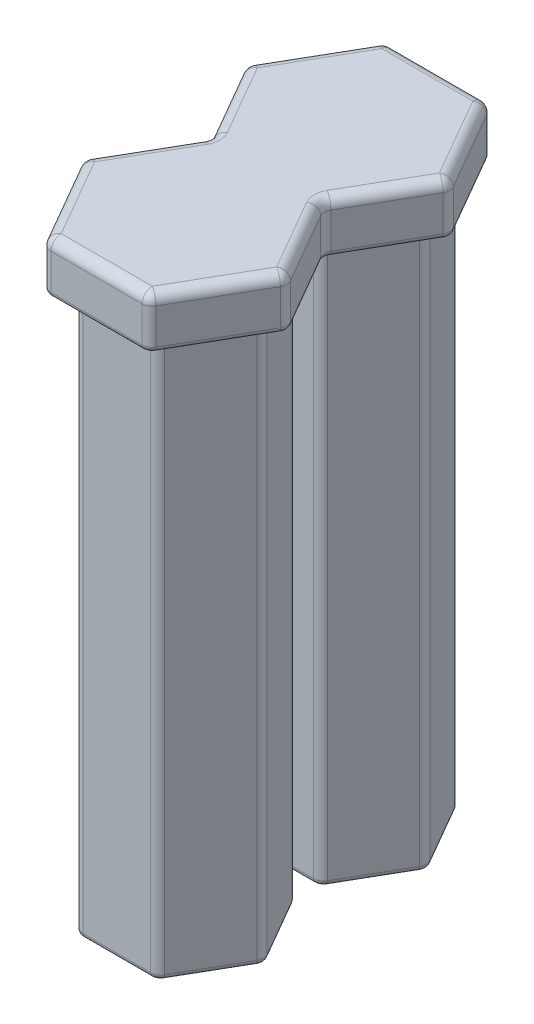
SolidWorks part; units mm, degrees
ref_plane "Front Plane" through (0, 0, 0) normal (0, 0, 1) x (1, 0, 0)
ref_plane "Top Plane" through (0, 0, 0) normal (0, 1, 0) x (1, 0, 0)
ref_plane "Right Plane" through (0, 0, 0) normal (1, 0, 0) x (0, 0, -1)
sketch "Sketch1" plane through (0, 0, 0) normal (0, 1, 0) x (1, 0, 0)
  line L0 (5.0518, -8.75) -> (10.1036, 0)
  line L1 (3.8971, -6.75) -> (7.7942, 0)
  line L2 (7.7942, 0) -> (3.8971, 6.75)
  line L3 (3.8971, 6.75) -> (-3.8971, 6.75)
  line L4 (-3.8971, 6.75) -> (-7.7942, 0)
  line L5 (-7.7942, 0) -> (-3.8971, -6.75)
  line L6 (-3.8971, -6.75) -> (3.8971, -6.75)
  line L7 (3.8971, 9.25) -> (7.7942, 16)
  line L8 (7.7942, 16) -> (3.8971, 22.75)
  line L9 (3.8971, 22.75) -> (-3.8971, 22.75)
  line L10 (-3.8971, 22.75) -> (-7.7942, 16)
  line L11 (-7.7942, 16) -> (-3.8971, 9.25)
  line L12 (-3.8971, 9.25) -> (3.8971, 9.25)
  line L13 (10.1036, 0) -> (5.4848, 8)
  line L15 (-5.4848, 8) -> (-10.1036, 0)
  line L16 (-10.1036, 0) -> (-5.0518, -8.75)
  line L17 (-5.0518, -8.75) -> (5.0518, -8.75)
  line L18 (5.4848, 8) -> (10.1036, 16)
  line L19 (10.1036, 16) -> (5.0518, 24.75)
  line L20 (5.0518, 24.75) -> (-5.0518, 24.75)
  line L21 (-5.0518, 24.75) -> (-10.1036, 16)
  line L22 (-10.1036, 16) -> (-5.4848, 8)
  line L24 (5.0518, 8.75) -> (-5.0518, 8.75) construction
  line L25 (-5.0518, 7.25) -> (5.0518, 7.25) construction
  line L26 (-10.1036, 16) -> (-5.0518, 7.25) construction
  line L27 (-5.0518, 8.75) -> (-10.1036, 0) construction
  line L28 (10.1036, 0) -> (5.0518, 8.75) construction
  line L29 (5.0518, 7.25) -> (10.1036, 16) construction
  circle A0 centre (0, 0) radius 6.75 construction
  circle A1 centre (0, 16) radius 6.75 construction
  dimension "D1" = 13.5
  dimension "D2" = 16
  dimension "D3" = 2
extrude "Boss-Extrude1" add sketch "Sketch1" along normal blind 55 contours L5 L6 L1 L2 L3 L4 | L7 L8 L9 L10 L11 L12 region at (0, 0, 0)
extrude "Boss-Extrude2" add sketch "Sketch1<4>" along normal blind 5 from surface contours L21 L22 L15 L16 L17 L0 L13 L18 L19 L20 L6 L5 L4 L3 L2 L1 L12 L11 L10 L9 L8 L7 | L11 L12 L7 L8 L9 L10 | L5 L6 L1 L2 L3 L4 region at (0, 0, -8) region at (0, 0, 0) region at (0, 0, -16) starting at face at (0, 55, -16)
sketch "Sketch1<4>" plane through (0, 0, 0) normal (0, 1, 0) x (1, 0, 0) same geometry as "Sketch1"
fillet "Fillet1" radius 1 20 edges at (10.1036, 57.5, -16) (5.0518, 57.5, -24.75) (-5.0518, 57.5, -24.75) (-10.1036, 57.5, -16) (-5.4848, 57.5, -8) (-10.1036, 57.5, 0) (-5.0518, 57.5, 8.75) (5.0518, 57.5, 8.75) (10.1036, 57.5, 0) (5.4848, 57.5, -8) (7.5777, 60, 4.375) (0, 60, 8.75) (-7.5777, 60, 4.375) (-7.7942, 60, -4) (-7.7942, 60, -12) (-7.5777, 60, -20.375) (0, 60, -24.75) (7.5777, 60, -20.375) (7.7942, 60, -12) (7.7942, 60, -4)
fillet "Fillet2" radius 1 12 edges at (3.8971, 27.5, -6.75) (7.7942, 27.5, 0) (3.8971, 27.5, 6.75) (-3.8971, 27.5, 6.75) (-7.7942, 27.5, 0) (-3.8971, 27.5, -6.75) (-3.8971, 27.5, -9.25) (3.8971, 27.5, -9.25) (7.7942, 27.5, -16) (3.8971, 27.5, -22.75) (-3.8971, 27.5, -22.75) (-7.7942, 27.5, -16)
sketch "Sketch2" plane through (0, 0, 0) normal (0, -1, 0) x (-1, 0, 0)
  point P0 (0, 16)
  point P1 (0, 0)
hole_wizard "Ø4.0mm Dowel Hole1" positions "Sketch2" profile "Sketch3" hole size "Ø4.0" standard "ISO"
sketch "Sketch3" plane through (0, 0, -16) normal (1, 0, 0) x (0, 0, -1)
  line L0 (0, 0) -> (0, 21.2017)
  line L1 (0, 21.2017) -> (2, 20)
  line L2 (2, 20) -> (2, 0)
  line L5 (2, 0) -> (0, 0)
  line L10 (0, 21.2017) -> (-2, 20) construction
  line L11 (0, -6.35) -> (0, 107.95) construction
  dimension "Hole Dia." = 4
  dimension "Hole Depth" = 20
  dimension "Drill Angle" = 118
fillet "Fillet3" radius 0.5 68 edges at (3.8198, 0, -22.616) (5.8457, 0, -19.375) (7.6395, 0, -16) (5.8457, 0, -12.625) (3.8198, 0, -9.384) (0, 0, -9.25) (-3.8198, 0, -9.384) (-5.8457, 0, -12.625) (-7.6395, 0, -16) (-5.8457, 0, -19.375) (-3.8198, 0, -22.616) (0, 0, -22.75) (-3.8198, 0, -6.616) (0, 0, -6.75) (3.8198, 0, -6.616) (5.8457, 0, -3.375) (7.6395, 0, 0) (5.8457, 0, 3.375) (3.8198, 0, 6.616) (0, 0, 6.75) (-3.8198, 0, 6.616) (-5.8457, 0, 3.375) (-7.6395, 0, 0) (-5.8457, 0, -3.375) (-3.8198, 55, -22.616) (0, 55, -22.75) (3.8198, 55, -22.616) (5.8457, 55, -19.375) (7.6395, 55, -16) (5.8457, 55, -12.625) (3.8198, 55, -9.384) (0, 55, -9.25) (-3.8198, 55, -9.384) (-5.8457, 55, -12.625) (-7.6395, 55, -16) (-5.8457, 55, -19.375) (-5.6395, 55, -8) (-7.7942, 55, -4) (-9.9489, 55, 0) (-7.5777, 55, 4.375) (-4.9745, 55, 8.616) (0, 55, 8.75) (4.9745, 55, 8.616) (7.5777, 55, 4.375) (9.9489, 55, 0) (7.7942, 55, -4) (5.6395, 55, -8) (7.7942, 55, -12) (9.9489, 55, -16) (7.5777, 55, -20.375) (4.9745, 55, -24.616) (0, 55, -24.75) (-4.9745, 55, -24.616) (-7.5777, 55, -20.375) (-9.9489, 55, -16) (-7.7942, 55, -12) (3.8198, 55, -6.616) (5.8457, 55, -3.375) (7.6395, 55, 0) (5.8457, 55, 3.375) (3.8198, 55, 6.616) (0, 55, 6.75) (-3.8198, 55, 6.616) (-5.8457, 55, 3.375) (-7.6395, 55, 0) (-5.8457, 55, -3.375) (-3.8198, 55, -6.616) (0, 55, -6.75)
